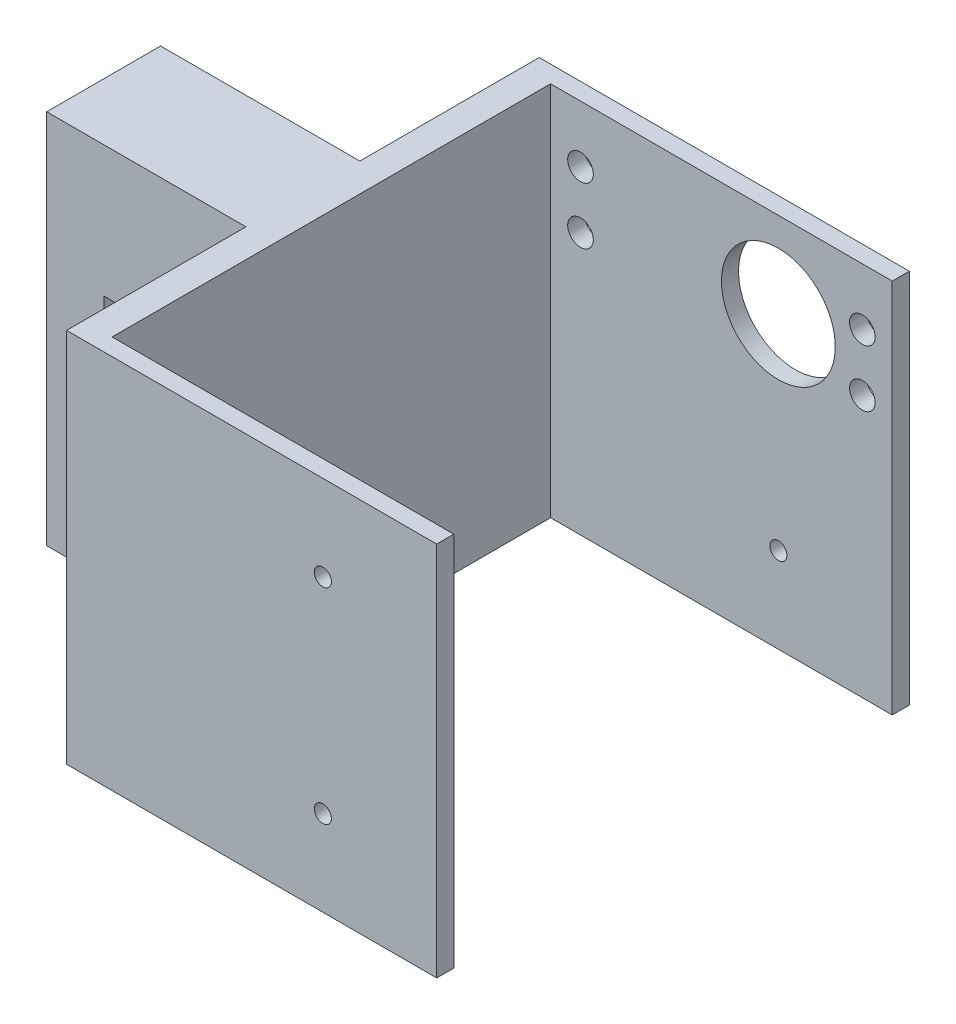
SolidWorks part; units mm, degrees
ref_plane "前视基准面" through (0, 0, 0) normal (0, 0, 1) x (1, 0, 0)
ref_plane "上视基准面" through (0, 0, 0) normal (0, 1, 0) x (1, 0, 0)
ref_plane "右视基准面" through (0, 0, 0) normal (1, 0, 0) x (0, 0, -1)
sketch "草图3" plane through (0, 0, 0) normal (0, 0, 1) x (1, 0, 0)
  line L0 (60.2665, 6.5325) -> (60.2665, 16.5325)
  line L1 (10.7665, 16.5325) -> (10.7665, 6.5325)
  line L2 (10.7665, 16.5325) -> (60.2665, 16.5325)
  circle A0 centre (60.2665, 16.5325) radius 3
  circle A1 centre (60.2665, 6.5325) radius 3
  circle A6 centre (10.7665, 6.5325) radius 3
  circle A7 centre (10.7665, 16.5325) radius 3
  dimension "D1" = 6
  dimension "D2" = 6
  dimension "D4" = 6
  dimension "D5" = 6
  dimension "D3" = 10
  dimension "D6" = 49.5
  dimension "D7" = 49.5
  dimension "D8" = 10
extrude "凸台-拉伸6" add sketch "草图3" along normal blind 0.001 contours A6 | A0 | A1 | A7
sketch "草图11" plane through (0, 0, 0.001) normal (0, 0, 1) x (1, 0, 0)
  circle A0 centre (10.7665, 16.5325) radius 2.25
  circle A1 centre (10.7665, 6.5325) radius 2.25
  circle A2 centre (60.2665, 16.5325) radius 2.25
  circle A3 centre (60.2665, 6.5325) radius 2.25
  dimension "D1" = 4.5
  dimension "D2" = 4.5
  dimension "D3" = 4.5
  dimension "D4" = 4.5
extrude "切除-拉伸2" cut sketch "草图11" against normal through all both and the other way through all
sketch "草图12" plane through (0, 0, 0.001) normal (0, 0, 1) x (1, 0, 0)
  line L4 (10.7665, 16.5325) -> (60.2665, 6.5325) construction
  line L5 (10.7665, 6.5325) -> (60.2665, 16.5325) construction
  line L6 (60.2665, 16.5325) -> (60.2665, 6.5325) construction
  line L7 (5.5165, 26.5325) -> (65.5165, 26.5325)
  line L8 (5.5165, 26.5325) -> (5.5165, 1.5325)
  line L9 (5.5165, -39.4675) -> (65.5165, -39.4675)
  line L10 (65.5165, 26.5325) -> (65.5165, -39.4675)
  line L11 (5.5165, 1.5325) -> (5.5165, -39.4675) construction
  line L13 (5.5165, -39.4675) -> (5.5165, 1.5325) construction
  line L16 (5.5165, 1.5325) -> (5.5165, -39.4675)
  circle A4 centre (45.5165, 11.5325) radius 10
  point P8 (35.5165, 11.5325)
  point P9 (35.5165, 26.5325)
  point P10 (-46.6091, 14.6442)
  point P11 (60.2665, 11.5325)
  dimension "D5" = 20
  dimension "D1" = 60
  dimension "D2" = 66
  dimension "D3" = 15
  dimension "D4" = 14.75
extrude "凸台-拉伸7" add sketch "草图12" along normal blind 3 contours L7 L10 L9 L16 L8
sketch "草图14" plane through (0, 0, 0.001) normal (0, 0, -1) x (-1, 0, 0)
  line L0 (-60.2665, 16.5325) -> (-60.2665, 6.5325) construction
  circle A1 centre (-60.2665, 6.5325) radius 2.25
  circle A2 centre (-60.2665, 16.5325) radius 2.25
  circle A6 centre (-10.7665, 6.5325) radius 2.25
  circle A7 centre (-10.7665, 16.5325) radius 2.25
  circle A8 centre (-45.5165, 11.5325) radius 10
  point P14 (-60.2665, 11.5325)
  point P15 (0.1696, -0.033)
  dimension "D2" = 20
extrude "切除-拉伸3" cut sketch "草图14" against normal blind 3
sketch "草图15" plane through (0, 0, 0.001) normal (0, 0, -1) x (-1, 0, 0)
  circle A0 centre (-45.5165, 11.5325) radius 10 construction
  circle A1 centre (-45.5165, 11.5325) radius 10
  circle A2 centre (-45.5165, -24.4675) radius 1.5
  dimension "D2" = 3
  dimension "D1" = 36
extrude "切除-拉伸4" cut sketch "草图15" against normal blind 65
sketch "草图17" plane through (0, 0, 3.001) normal (0, 0, 1) x (1, 0, 0)
  circle A0 centre (45.5165, -24.4675) radius 7.5
  circle A1 centre (45.5165, -24.4675) radius 5.5
  dimension "D1" = 15
  dimension "D2" = 2
extrude "凸台-拉伸8" add sketch "草图17" against normal blind 7
extrude "凸台-拉伸10" add sketch "草图12<4>" along normal blind 83
sketch "草图12<4>" plane through (0, 0, 0.001) normal (0, 0, 1) x (1, 0, 0) same geometry as "草图12"
sketch "草图19" plane through (65.5165, 0, 0) normal (1, 0, 0) x (0, 0, -1)
  line L0 (-83.001, 26.5325) -> (-80.001, 26.5325)
  line L1 (-83.001, 26.5325) -> (-0.001, 26.5325) construction
  line L2 (-0.001, 26.5325) -> (-3.001, 26.5325)
  dimension "D1" = 3
  dimension "D2" = 3
sketch "草图20" plane through (65.5165, 0, 0) normal (1, 0, 0) x (0, 0, -1)
  line L0 (-80.001, 26.5325) -> (-80.001, -39.4675)
  line L1 (-83.001, -39.4675) -> (-0.001, -39.4675) construction
  line L2 (-80.001, 26.5325) -> (-3.001, 26.5325)
  line L3 (-3.001, 26.5325) -> (-3.001, -39.4675)
  line L4 (-3.001, -39.4675) -> (-80.001, -39.4675)
extrude "切除-拉伸6" cut sketch "草图20" against normal blind 60
sketch "草图21" plane through (5.5165, 0, 0) normal (-1, 0, 0) x (0, 0, 1)
  line L0 (0.001, -39.4675) -> (83.001, -39.4675)
  line L1 (83.001, -39.4675) -> (83.001, 26.5325)
  line L2 (83.001, 26.5325) -> (0.001, 26.5325)
  line L3 (0.001, 26.5325) -> (0.001, -39.4675)
extrude "凸台-拉伸11" add sketch "草图21" along normal blind 40
extrude "切除-拉伸7" cut sketch "草图14<3>" against normal blind 40
sketch "草图14<3>" plane through (0, 0, 0.001) normal (0, 0, -1) x (-1, 0, 0) same geometry as "草图14"
sketch "草图22" plane through (0, 0, 3.001) normal (0, 0, 1) x (1, 0, 0)
  circle A0 centre (45.5165, 11.5325) radius 1.5
  circle A1 centre (45.5165, -24.4675) radius 1.5
  dimension "D1" = 36
sketch "草图23" plane through (0, 0, 83.001) normal (0, 0, 1) x (1, 0, 0)
  circle A0 centre (45.5165, 11.5325) radius 10
extrude "凸台-拉伸12" add sketch "草图23" against normal blind 3
extrude "切除-拉伸9" cut sketch "草图22" along normal blind 100 and the other way blind 100
sketch "草图25" plane through (0, 0, 0.001) normal (0, 0, -1) x (-1, 0, 0)
  line L5 (4.4334, 3.5325) -> (24.4334, 3.5325)
  line L6 (4.4334, 3.5325) -> (4.4334, -16.4675)
  line L7 (4.4334, -16.4675) -> (24.4334, -16.4675)
  line L8 (24.4334, 3.5325) -> (24.4334, -16.4675)
  line L9 (4.4334, 3.5325) -> (24.4334, -16.4675) construction
  line L10 (4.4334, -16.4675) -> (24.4334, 3.5325) construction
  point P10 (14.4334, -6.4675)
  dimension "D1" = 20
  dimension "D2" = 20
extrude "切除-拉伸10" cut sketch "草图25" against normal blind 100
sketch "草图28" plane through (0, -39.4675, 0) normal (0, -1, 0) x (1, 0, 0)
  line L7 (-34.4835, 31.501) -> (0.5165, 31.501)
  line L12 (-34.4835, 83.001) -> (0.5165, 83.001)
  line L13 (-34.4835, 83.001) -> (-34.4835, 51.501)
  line L14 (-34.4835, 51.501) -> (0.5165, 51.501)
  line L15 (0.5165, 83.001) -> (0.5165, 51.501)
  line L16 (-34.4835, 31.501) -> (-34.4835, 0.001)
  line L17 (-34.4835, 0.001) -> (0.5165, 0.001)
  line L18 (0.5165, 31.501) -> (0.5165, 0.001)
  dimension "D1" = 31.5
  dimension "D2" = 5
  dimension "D3" = 31.5
extrude "切除-拉伸12" cut sketch "草图28" against normal through all
